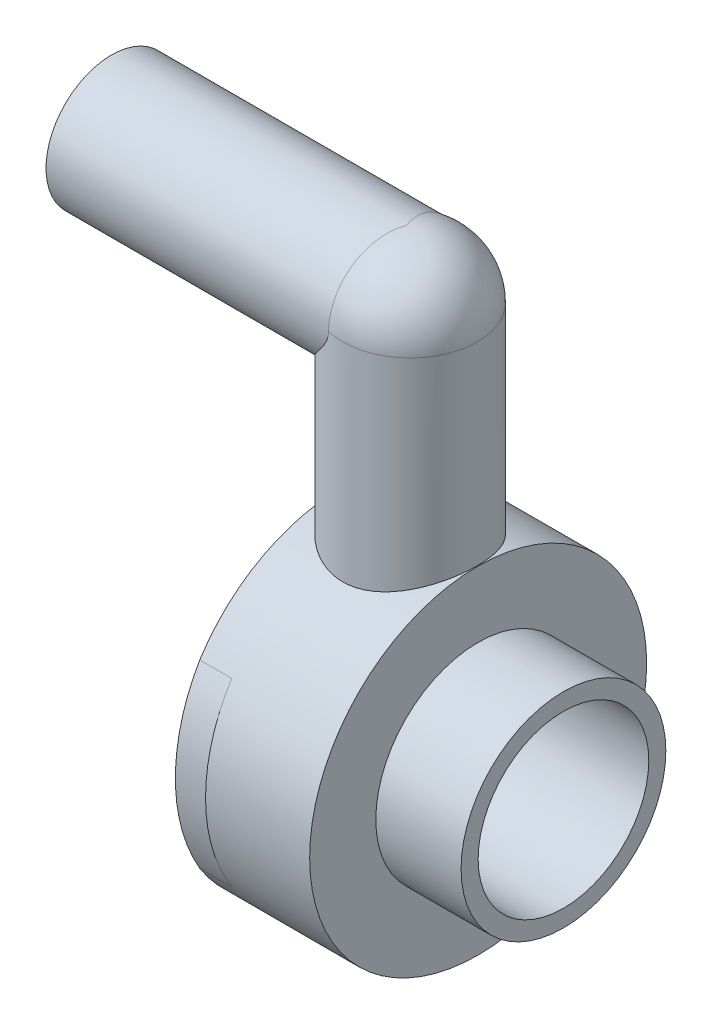
SolidWorks part; units mm, degrees
ref_plane "Front Plane" through (0, 0, 0) normal (0, 0, 1) x (1, 0, 0)
ref_plane "Top Plane" through (0, 0, 0) normal (0, 1, 0) x (1, 0, 0)
ref_plane "Right Plane" through (0, 0, 0) normal (1, 0, 0) x (0, 0, -1)
sketch "CircularBase" plane through (0, 0, 0) normal (0, 0, 1) x (1, 0, 0)
  line L0 (-5.0594, 0) -> (7.0797, 0) construction
  line L1 (0, 0) -> (0, 0.5)
  line L2 (0, 0.5) -> (-2, 0.5)
  line L3 (-2, 0.5) -> (-2, 2)
  line L4 (-2, 2) -> (-1.25, 2)
  line L5 (-1.25, 2) -> (-1.25, 1.5)
  line L6 (-1.25, 1.5) -> (5.15, 1.5)
  line L7 (5.15, 1.5) -> (5.15, 2.5)
  line L8 (5.15, 2.5) -> (5.9, 2.5)
  line L9 (5.9, 2.5) -> (5.9, 0)
  line L11 (0, 0) -> (5.9, 0)
  line L12 (7.0797, 0) -> (14.1483, 0) construction
  dimension "D1" = 0.75
  dimension "D2" = 0.75
  dimension "D3" = 1
  dimension "D4" = 0.5
  dimension "D5" = 1.5
  dimension "D6" = 0.5
  dimension "D7" = 2.5
  dimension "D8" = 2
  dimension "D9" = 5.9
revolve "CircularBaseRevolve" add sketch "CircularBase" angle 360 about L12
ref_plane "BasePlane" through (-2, 0, 0) normal (-1, 0, 0) x (0, 0, 1)
sketch "NotchCutSketc" plane through (-2, 0, 0) normal (-1, 0, 0) x (0, 0, 1)
  line L0 (0, 2) -> (0, -2) construction
  line L1 (-0.5, 0) -> (-0.5, 1.9365)
  line L2 (-0.5, 1.9365) -> (0.5, 1.9365)
  line L3 (-0.5, 0) -> (-0.5, -1.9365)
  line L4 (-0.5, -1.9365) -> (0.5, -1.9365)
  line L5 (0.5, 0) -> (0.5, -1.9365)
  line L6 (0.5, 0) -> (0.5, 1.9365)
  circle A0 centre (0, 0) radius 2 construction
  circle A1 centre (0, 0) radius 0.5 construction
  circle A2 centre (0, 0) radius 0.5 construction
  point P15 (0, -1.9365)
  point P17 (0, 1.9365)
extrude "NotchCut" cut sketch "NotchCutSketc" against normal blind 3
fillet "InsideNotchFillet1" radius 0.4 1 edges at (1, 0, -0.5) type face fillet first side face at (-0.875, 0, -0.5) second side face at (1, 0, 0)
fillet "InsideNotchFillet2" radius 0.4 1 edges at (1, 0, 0.5) type face fillet first side face at (-0.875, 0, 0.5) second side face at (1, 0, 0.2021)
fillet "OutsideNotchFillet" radius 0.1 16 edges at (-2, 0, 0.5) (-2, 0, -0.5) (-0.325, -1.4142, -0.5) (0.915, -1.4594, -0.3465) (1, -1.5, 0) (0.8413, -1.4403, 0.419) (-0.325, 1.4142, 0.5) (0.915, 1.4594, 0.3465) (1, 1.5, 0) (0.8413, 1.4403, -0.419) (-1.625, 1.9365, 0.5) (-1.625, 1.9365, -0.5) (-1.625, -1.9365, -0.5) (-0.325, -1.4142, 0.5) (-0.325, 1.4142, -0.5) (-1.25, -1.6754, 0.5)
ref_plane "TopBasePlane" through (5.9, 0, 0) normal (1, 0, 0) x (0, 0, -1)
sketch "TopCircularBaseExtrudeSketch" plane through (5.9, 0, 0) normal (1, 0, 0) x (0, 0, -1)
  line L0 (0, 2.007) -> (0, -2.007) construction
  line L13 (-2.0033, 0) -> (2.0033, 0) construction
  line L16 (-2.0033, -0.7505) -> (-2.0033, 0.7505)
  line L17 (-2.0033, 0.7505) -> (-0.7468, 0.7505)
  line L18 (0.7468, 2.007) -> (-0.7468, 2.007)
  line L19 (-0.7468, 2.007) -> (-0.7468, 0.7505)
  line L20 (2.0033, -0.7505) -> (2.0033, 0.7505)
  line L21 (2.0033, 0.7505) -> (0.7468, 0.7505)
  line L22 (0.7468, 2.007) -> (0.7468, 0.7505)
  line L23 (2.0033, -0.7505) -> (0.7468, -0.7505)
  line L24 (0.7468, -2.007) -> (0.7468, -0.7505)
  line L25 (-2.0033, -0.7505) -> (-0.7468, -0.7505)
  line L26 (-0.7468, -2.007) -> (-0.7468, -0.7505)
  line L27 (0.7468, -2.007) -> (-0.7468, -2.007)
  point P16 (2.0033, 0)
extrude "TopCircularBaseExtrude" add sketch "TopCircularBaseExtrudeSketch" along normal blind 7.9
fillet "TopCircularBaseFillet" radius 0.4 12 edges at (13.8, 1.3788, 0.7468) (13.8, 1.3788, -0.7468) (13.8, 0.7505, 1.375) (13.8, 0.7505, -1.375) (13.8, 0, -2.0033) (13.8, -0.7505, -1.375) (13.8, -1.3788, -0.7468) (13.8, -2.007, 0) (13.8, 0, 2.0033) (13.8, 2.007, 0) (13.8, -0.7505, 1.375) (13.8, -1.3788, 0.7468)
fillet "TopCircularbaseSideFillet" radius 0.1 36 edges at (5.9, 1.3788, 0.7468) (5.9, -2.007, 0) (5.9, -0.7505, -1.375) (5.9, 0.7505, -1.375) (5.9, 2.007, 0) (5.9, 0.7505, 1.375) (5.9, -0.7505, 1.375) (13.6828, -1.8899, -0.6296) (13.6828, -0.6334, -0.6296) (13.6828, -0.6334, 0.6296) (13.6828, -1.8899, 0.6296) (13.6828, -0.6334, -1.8861) (13.6828, 0.6334, -1.8861) (13.6828, 0.6334, -0.6296) (13.6828, 1.8899, -0.6296) (13.6828, 0.6334, 1.8861) (13.6828, 0.6334, 0.6296) (13.6828, 1.8899, 0.6296) (13.6828, -0.6334, 1.8861) (5.9, -1.3788, -0.7468) (9.65, -2.007, -0.7468) (9.65, -0.7505, -0.7468) (5.9, -1.3788, 0.7468) (9.65, -0.7505, 0.7468) (9.65, -2.007, 0.7468) (5.9, 0, -2.0033) (9.65, -0.7505, -2.0033) (9.65, 0.7505, -2.0033) (5.9, 1.3788, -0.7468) (9.65, 0.7505, -0.7468) (9.65, 2.007, -0.7468) (5.9, 0, 2.0033) (9.65, 0.7505, 2.0033) (9.65, 0.7505, 0.7468) (9.65, 2.007, 0.7468) (9.65, -0.7505, 2.0033)
ref_plane "Plane1" [suppressed] through (0, -2.007, 0) normal (0, -1, 0) x (-1, 0, 0)
sketch "CircularTipSketch" [suppressed] plane through (0, -2.007, 0) normal (0, -1, 0) x (-1, 0, 0)
  line L0 (-6, 2.0033) -> (-6, -2.0033)
  line L1 (-6, -2.0033) -> (-6, -2.5355)
  line L2 (-6, -2.5355) -> (2.115, -2.5355)
  line L3 (2.115, -2.5355) -> (1.9623, 2.8509)
  line L4 (1.9623, 2.8509) -> (-6, 2.7898)
  line L5 (-6, 2.7898) -> (-6, 2.0033)
extrude "CircularTip" [suppressed] cut sketch "CircularTipSketch" against normal through all
ref_plane "Plane2" [suppressed] through (6, 0, 0) normal (-1, 0, 0) x (0, 0, 1)
mirror "Mirror2" [suppressed]
ref_plane "Plane3" through (0, 2.007, 0) normal (0, 1, 0) x (1, 0, 0)
sketch "BaseCutSketch" plane through (0, 2.007, 0) normal (0, 1, 0) x (1, 0, 0)
  line L0 (5.15, 2.5558) -> (5.15, -2.5)
  line L1 (5.15, -2.5) -> (-2.0426, -2.5)
  line L2 (-2.0426, -2.5) -> (-2.0426, 2.5558)
  line L3 (-2.0426, 2.5558) -> (5.15, 2.5558)
extrude "BaseCut" cut sketch "BaseCutSketch" against normal through all contours L3 L2 L1 L0 region at (1.5537, 2.007, -0.0279)
ref_plane "Plane4" through (13.8, 0, 0) normal (1, 0, 0) x (0, 0, -1)
sketch "NotchCutSketch" plane through (0, 0, 0) normal (0, 1, 0) x (1, 0, 0)
  line L7 (7.7505, 3.747) -> (7.7505, 0)
  line L14 (7.7505, 0) -> (10.818, 0) construction
  line L19 (7.7505, 0) -> (5.15, 0)
  line L20 (5.15, 2.5) -> (5.15, -2.5) construction
  line L21 (5.15, 0) -> (5.15, 4)
  line L22 (5.15, 4) -> (6.4505, 4)
  line L23 (6.4505, 4) -> (6.4505, 3.747)
  line L24 (6.4505, 3.747) -> (7.7505, 3.747)
  point P16 (7.1, 2.25)
  dimension "D1" = 1.3
  dimension "D2" = 4
revolve "CircularEvolveWithNotch" [suppressed] add sketch "NotchCutSketch" angle 360 about L14
ref_plane "Plane5" through (5.15, 0, 0) normal (-1, 0, 0) x (0, 0, 1)
sketch "CrossHoleCutSketch" plane through (5.15, 0, 0) normal (-1, 0, 0) x (0, 0, 1)
  line L0 (-0.8429, 0.8584) -> (-0.8429, 1.9149)
  line L1 (-0.6429, 2.1149) -> (0.6506, 2.1149)
  line L2 (0.8506, 1.9149) -> (0.8506, 0.8584)
  line L3 (0.8506, 0.8584) -> (1.9071, 0.8584)
  line L4 (-1.8994, 0.8584) -> (-0.8429, 0.8584)
  line L5 (-0.8429, -0.8427) -> (-1.8994, -0.8427)
  line L6 (-0.8429, -0.8427) -> (-0.8429, -1.8992)
  line L7 (-0.6429, -2.0992) -> (0.6506, -2.0992)
  line L8 (0.8506, -1.8992) -> (0.8506, -0.8427)
  line L9 (0.8506, -0.8427) -> (1.9071, -0.8427)
  line L10 (2.1071, -0.6427) -> (2.1071, 0.6584)
  line L11 (-2.0994, -0.6427) -> (-2.0994, 0.6584)
  arc A0 (-0.8429, 1.9149) -> (-0.6429, 2.1149) centre (-0.6429, 1.9149) cw
  arc A1 (0.8506, 1.9149) -> (0.6506, 2.1149) centre (0.6506, 1.9149) ccw
  arc A2 (1.9071, 0.8584) -> (2.1071, 0.6584) centre (1.9071, 0.6584) cw
  arc A3 (1.9071, -0.8427) -> (2.1071, -0.6427) centre (1.9071, -0.6427) ccw
  arc A4 (0.8506, -1.8992) -> (0.6506, -2.0992) centre (0.6506, -1.8992) cw
  arc A5 (-0.6429, -2.0992) -> (-0.8429, -1.8992) centre (-0.6429, -1.8992) cw
  arc A6 (-1.8994, -0.8427) -> (-2.0994, -0.6427) centre (-1.8994, -0.6427) cw
  arc A7 (-1.8994, 0.8584) -> (-2.0994, 0.6584) centre (-1.8994, 0.6584) ccw
extrude "CrossHoleCut" [suppressed] cut sketch "CrossHoleCutSketch" against normal through all
ref_plane "Plane11" [suppressed] through (7.7505, 0, 0) normal (1, 0, 0) x (0, 0, -1)
sketch "Sketch16" [suppressed] plane through (7.7505, 0, 0) normal (1, 0, 0) x (0, 0, -1)
  line L1 (0.8429, 0.8584) -> (0.8429, 1.9149)
  line L3 (-0.8506, 0.8584) -> (-1.9071, 0.8584)
  line L4 (-2.1071, 0.6584) -> (-2.1071, -0.6427)
  line L5 (-1.9071, -0.8427) -> (-0.8506, -0.8427)
  line L6 (-0.8506, -0.8427) -> (-0.8506, -1.8992)
  line L7 (0.8429, -1.8992) -> (0.8429, -0.8427)
  line L8 (0.8429, -0.8427) -> (1.8994, -0.8427)
  line L9 (2.0994, -0.6427) -> (2.0994, 0.7075)
  line L10 (0.8429, 0.8584) -> (1.8994, 0.8584)
  line L11 (-0.6506, -2.0992) -> (0.6429, -2.0992)
  line L12 (-0.8506, 0.8584) -> (-0.8506, 1.9149)
  line L13 (-0.6506, 2.1149) -> (0.6429, 2.1149)
  circle A0 centre (0, 0) radius 4
  arc A1 (-1.9071, -0.8427) -> (-2.1071, -0.6427) centre (-1.9071, -0.6427) cw
  arc A2 (-2.1071, 0.6584) -> (-1.9071, 0.8584) centre (-1.9071, 0.6584) cw
  arc A6 (1.8994, 0.8584) -> (2.0994, 0.7075) centre (1.8994, 0.6504) cw
  arc A7 (2.0994, -0.6427) -> (1.8994, -0.8427) centre (1.8994, -0.6427) cw
  arc A8 (0.8429, -1.8992) -> (0.6429, -2.0992) centre (0.6429, -1.8992) cw
  arc A9 (-0.8506, -1.8992) -> (-0.6506, -2.0992) centre (-0.6506, -1.8992) ccw
  arc A10 (-0.8506, 1.9149) -> (-0.6506, 2.1149) centre (-0.6506, 1.9149) cw
  arc A11 (0.8429, 1.9149) -> (0.6429, 2.1149) centre (0.6429, 1.9149) ccw
extrude "CircularCrossHolwCircle" [suppressed] add sketch "Sketch16" along normal blind 1.25
fillet "EdgesFillet" [suppressed] radius 0.1
fillet "Fillet2" [suppressed] radius 0.1
ref_plane "Plane6" through (0, 0, -2.0033) normal (0, 0, -1) x (-1, 0, 0)
sketch "Sketch1" plane through (0, 0, -2.0033) normal (0, 0, -1) x (-1, 0, 0)
  line L0 (-5.9, 2.5) -> (-5.9, -2.5)
  line L1 (-5.9, 2.5) -> (-5.9, -2.5) construction
  line L2 (-5.9, -2.5) -> (-13.8486, -2.5)
  line L3 (-13.8486, -2.5) -> (-13.8486, 2.5)
  line L4 (-13.8486, 2.5) -> (-5.9, 2.5)
extrude "RemovedMaterial" cut sketch "Sketch1" against normal through all
sketch "Sketch2" plane through (0, 0, -2.0033) normal (0, 0, -1) x (-1, 0, 0)
  line L1 (-11.5273, 0) -> (-12.3621, 0) construction
  line L2 (-5.15, 3.95) -> (-5.15, 0.25)
  line L3 (-5.15, 3.95) -> (-8.341, 3.95)
  line L4 (-8.341, 1.2482) -> (-11.5214, 1.2482)
  line L6 (-11.5214, 1.2482) -> (-11.5214, 0.25)
  line L8 (-8.341, 3.95) -> (-8.341, 1.2482)
  line L10 (-5.15, -2.5) -> (-5.15, 2.5) construction
  line L11 (-5.15, 0.25) -> (-11.5214, 0.25)
  dimension "D1" = 3.7
revolve "Revolve2" add sketch "Sketch2" angle 360 about L1
ref_plane "Plane8" through (5.9, 0, 0) normal (1, 0, 0) x (0, 0, -1)
sketch "Sketch13" plane through (5.9, 0, 0) normal (1, 0, 0) x (0, 0, -1)
  arc A0 (-1.3327, 2.1152) -> (-1.3327, -2.1152) centre (0, 0) ccw
  arc A2 (-1.3327, 2.1152) -> (-1.3327, -2.1152) centre (2.2958, 0) ccw
  dimension "D1" = 2.5
extrude "RemovedMaterial2" cut sketch "Sketch13" against normal through all
sketch "Sketch14" plane through (5.9, 0, 0) normal (1, 0, 0) x (0, 0, -1)
  line L0 (2.0033, -0.25) -> (2.0033, 0.25) construction
  circle A0 centre (2.0033, 0) radius 0.2516
ref_plane "ShellPlane" through (5.15, 0, 0) normal (-1, 0, 0) x (0, 0, 1)
sketch "ShellSketch" plane through (5.15, 0, 0) normal (-1, 0, 0) x (0, 0, 1)
  circle A0 centre (-2.0033, 0) radius 1.9017
extrude "ShellFeature" cut sketch "ShellSketch" against normal blind 1.6
ref_plane "Plane13" through (8.341, 0, 0) normal (1, 0, 0) x (0, 0, -1)
sketch "RemoveMaterialSketch3" plane through (8.341, 0, 0) normal (1, 0, 0) x (0, 0, -1)
  circle A0 centre (2.0033, 0) radius 1.2482
extrude "RemoveMaterial3" cut sketch "RemoveMaterialSketch3" along normal through all
sketch "Sketch21" plane through (8.341, 0, 0) normal (1, 0, 0) x (0, 0, -1)
  circle A0 centre (2.0033, 0) radius 2.4
  circle A1 centre (2.0033, 0) radius 2
  dimension "D1" = 4.8
  dimension "D2" = 4
extrude "CylindereExtrudeVertical" add sketch "Sketch21" along normal blind 2
sketch "ThroughHoleSketch" plane through (8.341, 0, 0) normal (1, 0, 0) x (0, 0, -1)
  circle A0 centre (2.0033, 0) radius 2
extrude "ThroughHole" cut sketch "ThroughHoleSketch" against normal through all
ref_plane "Plane14" through (5.15, 0, 0) normal (-1, 0, 0) x (0, 0, 1)
sketch "Sketch23" plane through (5.15, 0, 0) normal (-1, 0, 0) x (0, 0, 1)
  circle A0 centre (-2.0033, 0) radius 2.4
  dimension "D1" = 4.8
extrude "Cut-Extrude6" cut sketch "Sketch23" against normal blind 1.6
ref_plane "BisectingPlane" through (6.7455, 0, 0) normal (1, 0, 0) x (0, 0, -1)
sketch "Sketch24" plane through (6.7455, 0, 0) normal (1, 0, 0) x (0, 0, -1)
  line L0 (2.0033, 0) -> (2.0033, 3.4935) construction
  line L2 (3.5835, 3.5518) -> (3.5835, 8.4935)
  line L4 (2.0033, 9.1481) -> (2.0033, 10.1942) construction
  line L5 (2.0033, 9.1481) -> (2.0033, 3.5518)
  line L6 (2.0033, 3.5518) -> (3.5835, 3.5518)
  arc A0 (2.0033, 9.1481) -> (3.5835, 8.4935) centre (2.0033, 6.9132) cw
  point P7 (2.0033, 3.4935)
revolve "CylinderRevolve" add sketch "Sketch24" angle 360 about L4
sketch "Sketch25" plane through (6.7455, 0, 0) normal (1, 0, 0) x (0, 0, -1)
  line L0 (2.0033, 3.95) -> (2.0033, 10.2085) construction
  line L1 (3.5835, 8.4935) -> (0.423, 8.4935) construction
  arc A0 (3.5835, 3.6201) -> (0.423, 3.6201) centre (2.0033, 0) ccw construction
  circle A1 centre (2.0033, 8.4935) radius 1.5349
extrude "Boss-Extrude3" add sketch "Sketch25" against normal blind 7
sketch "Sketch27" plane through (6.7455, 0, 0) normal (1, 0, 0) x (0, 0, -1)
  line L0 (2.0033, 8.4935) -> (2.0033, 10.0284)
  line L1 (3.5835, 8.4935) -> (0.423, 8.4935) construction
  line L2 (2.0033, 8.4935) -> (0.423, 8.4935)
  line L3 (2.0033, 10.379) -> (2.0033, 10.0284) construction
  arc A0 (3.5376, 8.5382) -> (0.469, 8.5382) centre (2.0033, 8.4935) ccw construction
  arc A1 (0.423, 8.4935) -> (2.0033, 10.0284) centre (1.9586, 8.4935) cw
revolve "Revolve4" add sketch "Sketch27" angle 360 about L3
ref_plane "Plane17" through (-0.2545, 0, 0) normal (-1, 0, 0) x (0, 0, 1)
sketch "Sketch28" plane through (-0.2545, 0, 0) normal (-1, 0, 0) x (0, 0, 1)
  line L0 (-2.0033, 10.0284) -> (-2.0033, 6.9586) construction
  line L1 (-3.5382, 8.4935) -> (-0.4683, 8.4935) construction
  arc A0 (-3.5382, 8.4935) -> (-0.4683, 8.4935) centre (-2.0033, 8.4935) ccw construction
  circle A1 centre (-2.0033, 8.4935) radius 0.5026
extrude "SmallHoleInCylinder" cut sketch "Sketch28" against normal blind 3
